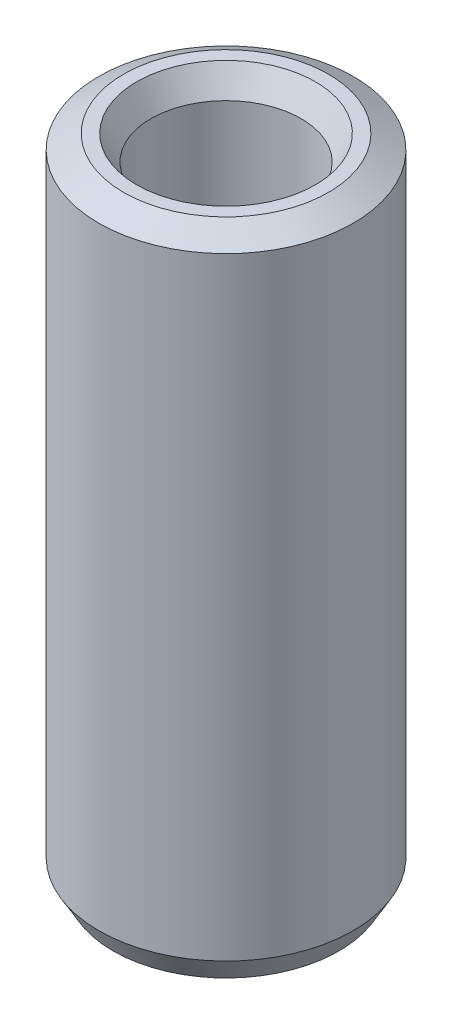
SolidWorks part; units mm, degrees
ref_plane "Front Plane" through (0, 0, 0) normal (0, 0, 1) x (1, 0, 0)
ref_plane "Top Plane" through (0, 0, 0) normal (0, 1, 0) x (1, 0, 0)
ref_plane "Right Plane" through (0, 0, 0) normal (1, 0, 0) x (0, 0, -1)
sketch "Sketch1" plane through (0, 0, 0) normal (0, 1, 0) x (1, 0, 0)
  circle A0 centre (0, 0) radius 12.5
  dimension "SLEEVE_OD" = 25
extrude "Boss-Extrude1" add sketch "Sketch1" along normal blind 64.0378
sketch "Sketch2" plane through (0, 0, 0) normal (0, 1, 0) x (1, 0, 0)
  circle A0 centre (0, 0) radius 7.3748
  dimension "BORE_D" = 14.7495
extrude "Cut-Extrude1" cut sketch "Sketch2" along normal through all
chamfer "Chamfer1" distance 1.4049 angle 60 4 edges at (0, 64.0378, 7.3748) (0, 0, 7.3748) (0, 0, 12.5) (0, 64.0378, 12.5) first distance on face at (0, 64.0378, 7.3748) first distance on face at (0, 0, 7.3748) first distance on face at (0, 64.0378, 12.5)
